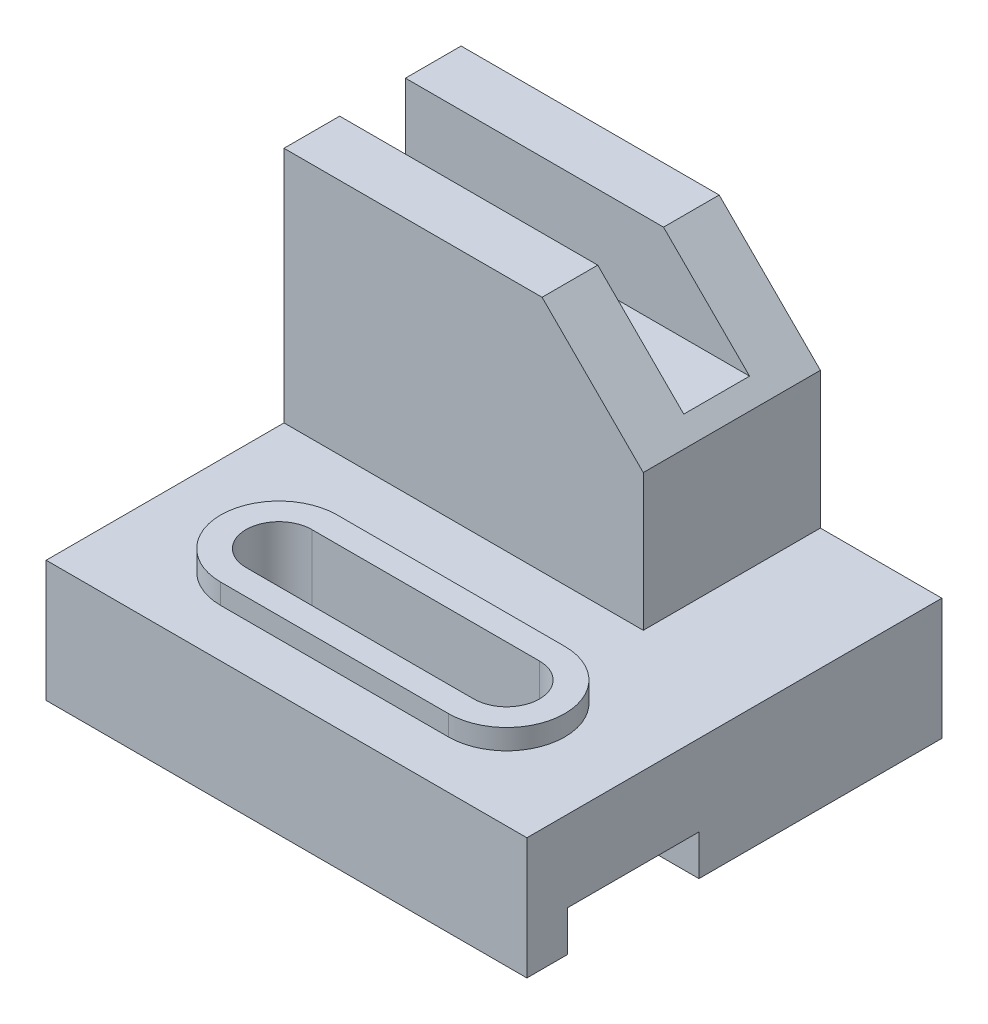
SolidWorks part; units mm, degrees
ref_plane "Front Plane" through (0, 0, 0) normal (0, 0, 1) x (1, 0, 0)
ref_plane "Top Plane" through (0, 0, 0) normal (0, 1, 0) x (1, 0, 0)
ref_plane "Right Plane" through (0, 0, 0) normal (1, 0, 0) x (0, 0, -1)
sketch "Sketch2" plane through (0, 0, 0) normal (1, 0, 0) x (0, 0, -1)
  line L0 (0, 0) -> (0, 24)
  line L1 (0, 24) -> (9.5, 24)
  line L2 (9.5, 24) -> (9.5, 28)
  line L3 (9.5, 28) -> (32.5, 28)
  line L4 (32.5, 28) -> (32.5, 24)
  line L5 (32.5, 24) -> (47, 24)
  line L6 (47, 24) -> (47, 71)
  line L7 (47, 71) -> (58, 71)
  line L8 (58, 71) -> (58, 54)
  line L9 (58, 54) -> (71, 54)
  line L10 (71, 54) -> (71, 71)
  line L11 (71, 71) -> (82, 71)
  line L12 (82, 71) -> (82, 0)
  line L13 (82, 0) -> (34, 0)
  line L14 (34, 0) -> (34, 8)
  line L15 (34, 8) -> (8, 8)
  line L16 (8, 8) -> (8, 0)
  line L17 (8, 0) -> (0, 0)
  line L18 (21, 28) -> (21, 4.2876) construction
  line L19 (64.5, 54) -> (64.5, 65.1429) construction
  dimension "D1" = 4
  dimension "D2" = 24
  dimension "D3" = 71
  dimension "D4" = 13
  dimension "D5" = 26
  dimension "D6" = 8
  dimension "D7" = 17
  dimension "D8" = 21
  dimension "D9" = 35
  dimension "D10" = 23
  dimension "D11" = 82
extrude "Boss-Extrude1" add sketch "Sketch2" along normal blind 95
sketch "Sketch3" plane through (0, 0, 0) normal (0, 0, 1) x (1, 0, 0)
  line L0 (71, 71) -> (95, 71)
  line L1 (0, 0) -> (95, 0)
  line L2 (0, 0) -> (0, 24)
  line L3 (0, 24) -> (95, 24)
  line L4 (95, 0) -> (95, 24)
  line L5 (0, 71) -> (71, 71)
  line L6 (0, 71) -> (0, 24)
  line L7 (0, 24) -> (71, 24)
  line L8 (71, 71) -> (71, 24)
  line L9 (95, 71) -> (95, 24)
  line M12 (95, 24) -> (0, 24)
  dimension "D1" = 71
extrude "Cut-Extrude2" cut sketch "Sketch3" against normal through all from offset 40 contours L9 L0 L8 M12 region at (83, 47.5, 0) offset against normal yes
chamfer "Chamfer2" distance 20 angle 45 1 edges at (71, 71, -52.5)
sketch "Sketch4" plane through (0, 28, 0) normal (0, 1, 0) x (1, 0, 0)
  line L0 (25, 32.5) -> (70, 32.5)
  line L1 (25, 9.5) -> (70, 9.5)
  line L2 (95, 9.5) -> (95, 0) construction
  line L3 (95, 9.5) -> (0, 9.5) construction
  line L4 (95, 32.5) -> (0, 32.5) construction
  line L5 (70, 9.5) -> (25, 9.5)
  line L6 (70, 32.5) -> (25, 32.5)
  line L7 (25, 27.5) -> (70, 27.5)
  line L8 (70, 14.5) -> (25, 14.5)
  line L9 (0, 32.5) -> (95, 32.5)
  line L10 (95, 32.5) -> (95, 9.5)
  line L11 (95, 9.5) -> (0, 9.5)
  line L12 (0, 9.5) -> (0, 32.5)
  arc A0 (70, 9.5) -> (70, 32.5) centre (70, 21) ccw
  arc A1 (25, 32.5) -> (25, 9.5) centre (25, 21) ccw
  arc A2 (25, 27.5) -> (25, 14.5) centre (25, 21) ccw
  arc A3 (70, 14.5) -> (70, 27.5) centre (70, 21) ccw
  dimension "D1" = 45
  dimension "D2" = 25
extrude "Cut-Extrude3" cut sketch "Sketch4" against normal up to surface (4 mm away) contours A1 L7 L2 L3 | A0 L3 L4 L7 region at (8.1903, 28, -21) region at (86.8097, 28, -21) up to face at (55.3333, 24, -53.8333)
extrude "Cut-Extrude4" cut sketch "Sketch4<3>" along direction (0, 1, 0) on the side against the normal up to surface (20 mm away) contours L8 A3 L7 A2 region at (47.5, 28, -21) up to face at (47.5, 8, -21)
sketch "Sketch4<3>" plane through (0, 28, 0) normal (0, 1, 0) x (1, 0, 0) same geometry as "Sketch4"
